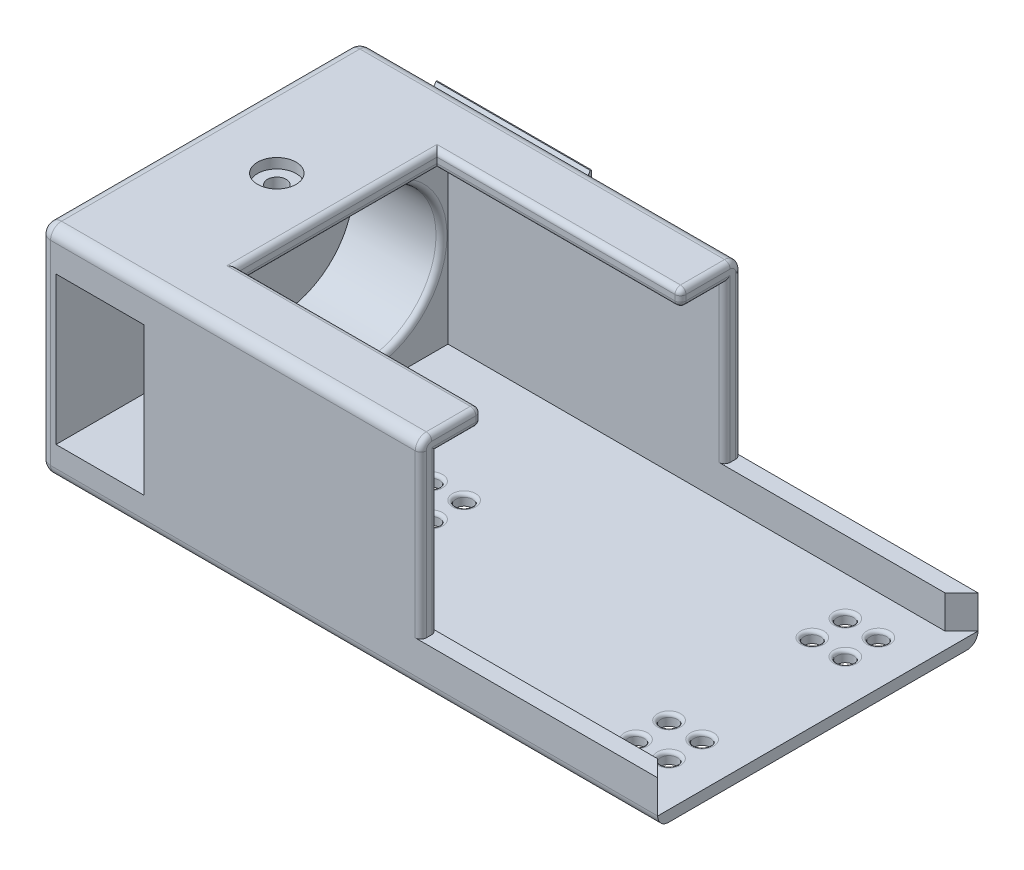
SolidWorks part; units mm, degrees
ref_plane "Front Plane" through (0, 0, 0) normal (0, 0, 1) x (1, 0, 0)
ref_plane "Top Plane" through (0, 0, 0) normal (0, 1, 0) x (1, 0, 0)
ref_plane "Right Plane" through (0, 0, 0) normal (1, 0, 0) x (0, 0, -1)
sketch "Sketch1" plane through (0, 0, 0) normal (0, 1, 0) x (1, 0, 0)
  line L1 (-26.2581, 9.1194) -> (18.3419, 9.1194) construction
  line L2 (-26.2581, 9.1194) -> (-26.2581, -16.5806) construction
  line L3 (-26.2581, -16.5806) -> (18.3419, -16.5806) construction
  line L4 (18.3419, 9.1194) -> (18.3419, -16.5806) construction
  line L5 (-26.5081, 9.2444) -> (18.5919, 9.2444)
  line L6 (-26.5081, 9.2444) -> (-26.5081, -16.8306)
  line L7 (-26.5081, -16.8306) -> (18.5919, -16.8306)
  line L8 (18.5919, 9.2444) -> (18.5919, -16.8306)
  line L9 (-28.0081, 10.7444) -> (20.0919, 10.7444)
  line L10 (-28.0081, 10.7444) -> (-28.0081, -18.3306)
  line L11 (-28.0081, -18.3306) -> (20.0919, -18.3306)
  line L12 (20.0919, 10.7444) -> (20.0919, -18.3306)
  dimension "D1" = 25.7
  dimension "D2" = 44.6
  dimension "D3" = 0.25
  dimension "D4" = 0.25
  dimension "D5" = 0.25
  dimension "D6" = 0.25
  dimension "D7" = 1.5
  dimension "D8" = 1.5
  dimension "D9" = 1.5
  dimension "D10" = 1.5
extrude "Boss-Extrude1" add sketch "Sketch1" along normal blind 1 contours L10 L11 L12 L9
sketch "Sketch3" plane through (0, 1, 0) normal (0, 1, 0) x (1, 0, 0)
  line L0 (-28.0081, 10.7444) -> (20.0919, 10.7444) construction
  line L1 (-26.5081, 9.2444) -> (18.5919, 9.2444)
  line L2 (-26.5081, 9.2444) -> (-26.5081, -16.8306)
  line L3 (-26.5081, -16.8306) -> (18.5919, -16.8306)
  line L5 (-28.0081, 10.7444) -> (-28.0081, -18.3306) construction
  line L7 (-28.0081, -18.3306) -> (20.0919, -18.3306) construction
  line L8 (18.5919, 9.2444) -> (20.0919, 10.7444)
  line L9 (-28.0081, 10.7444) -> (20.0919, 10.7444)
  line L10 (-28.0081, 10.7444) -> (-28.0081, -18.3306)
  line L11 (-28.0081, -18.3306) -> (20.0919, -18.3306)
  line L13 (18.5919, -16.8306) -> (20.0919, -18.3306)
  dimension "D1" = 1.5
  dimension "D2" = 1.5
  dimension "D4" = 1.5
extrude "Boss-Extrude3" add sketch "Sketch3" along normal blind 3
sketch "Sketch6" plane through (0, 4, 0) normal (0, 1, 0) x (1, 0, 0)
  line L0 (-28.0081, -18.3306) -> (20.0919, -18.3306) construction
  line L1 (-28.0081, 10.7444) -> (-1.4081, 10.7444)
  line L2 (-28.0081, 10.7444) -> (-28.0081, -18.3306)
  line L3 (-28.0081, -18.3306) -> (-1.4081, -18.3306)
  line L4 (-1.4081, 10.7444) -> (-1.4081, 9.2444)
  line L5 (-26.5081, -16.8306) -> (-26.5081, 9.2444) construction
  line L6 (-26.5081, 9.2444) -> (-1.4081, 9.2444)
  line L7 (-26.5081, 9.2444) -> (-26.5081, -16.8306)
  line L8 (-26.5081, -16.8306) -> (-1.4081, -16.8306)
  line L10 (-26.5081, -16.8306) -> (-26.5081, 9.2444) construction
  line L11 (18.5919, -16.8306) -> (-26.5081, -16.8306) construction
  line L12 (-26.5081, 9.2444) -> (18.5919, 9.2444) construction
  line L13 (-1.4081, -16.8306) -> (-1.4081, -18.3306)
  dimension "D1" = 20
extrude "Boss-Extrude4" add sketch "Sketch6" along normal blind 17.2 from surface at -3 starting at face at (4.0585, 1, 3.7931)
sketch "Sketch7" plane through (0, 18.2, 0) normal (0, 1, 0) x (1, 0, 0)
  line L0 (-1.4081, -18.3306) -> (-28.0081, -18.3306) construction
  line L1 (-28.0081, 10.7444) -> (-1.4081, 10.7444)
  line L2 (-28.0081, 10.7444) -> (-28.0081, -18.3306)
  line L3 (-28.0081, -18.3306) -> (-1.4081, -18.3306)
  line L4 (-1.4081, 10.7444) -> (-1.4081, -18.3306)
  line L5 (-1.4081, -16.8306) -> (-1.4081, -18.3306) construction
extrude "Boss-Extrude5" add sketch "Sketch7" along normal blind 1.5
sketch "Sketch8" plane through (-28.0081, 0, 0) normal (-1, 0, 0) x (0, 0, 1)
  line L0 (-9.2444, 1) -> (16.8306, 1) construction
  line L3 (16.8306, 18.2) -> (-9.2444, 18.2) construction
  line L4 (-10.7444, 19.7) -> (-10.7444, 0) construction
  line L5 (18.3306, 19.7) -> (18.3306, 0) construction
  line L6 (-10.7444, 19.7) -> (18.3306, 19.7) construction
  line L7 (-10.7444, 0) -> (18.3306, 0) construction
  line L8 (-9.2444, 18.2) -> (-9.2444, 1) construction
  line L9 (16.8306, 18.2) -> (16.8306, 1) construction
  line L10 (3.7931, 18.2) -> (3.7931, 1) construction
  line L11 (-9.2444, 9.6) -> (16.8306, 9.6) construction
  line L12 (-8.6569, 9.6) -> (16.2431, 9.6) construction
  line L15 (-1.9569, 9.6) -> (9.5431, 9.6) construction
  line L16 (-1.9569, 16.3) -> (9.5431, 16.3)
  line L17 (-1.9569, 2.9) -> (9.5431, 2.9)
  line L19 (9.5431, 16.3) -> (18.3306, 16.3)
  line L20 (9.5431, 16.3) -> (9.5431, 2.9) construction
  line L21 (9.5431, 2.9) -> (18.3306, 2.9)
  line L22 (18.3306, 16.3) -> (18.3306, 2.9)
  arc A2 (-1.9569, 16.3) -> (-1.9569, 2.9) centre (-1.9569, 9.6) ccw
  point P15 (3.7931, 18.2)
  point P18 (3.7931, 19.7)
  point P29 (3.7931, 9.6)
  dimension "D3" = 1.5
  dimension "D4" = 1.5
  dimension "D5" = 1.5
  dimension "D1" = 1
  dimension "D2" = 1.5
  dimension "D6" = 1.5
  dimension "D9" = 13.4
  dimension "D7" = 24.9
  dimension "D8" = 0.5875
  dimension "D10" = 1.9
  dimension "D11" = 7.2875
extrude "Cut-Extrude2" cut sketch "Sketch8" against normal blind 1.5
sketch "Sketch17" plane through (-28.0081, 0, 0) normal (-1, 0, 0) x (0, 0, 1)
  line L1 (-10.7444, 19.7) -> (18.3306, 19.7)
  line L2 (-10.7444, 19.7) -> (-10.7444, 0)
  line L3 (-10.7444, 0) -> (18.3306, 0)
  line L4 (18.3306, 19.7) -> (18.3306, 0)
  line L5 (-1.9569, 16.3) -> (18.3306, 16.3)
  line L7 (-1.9569, 2.9) -> (18.3306, 2.9)
  line L8 (18.3306, 16.3) -> (18.3306, 2.9)
  arc A0 (-1.9569, 16.3) -> (-1.9569, 2.9) centre (-1.9569, 9.6) ccw
  arc M6 (-1.9569, 2.9) -> (-1.9569, 16.3) centre (-1.9569, 9.6) cw
  line M7 (-1.9569, 16.3) -> (18.3306, 16.3)
  line M8 (18.3306, 16.3) -> (18.3306, 19.7)
  line M9 (18.3306, 19.7) -> (-10.7444, 19.7)
  line M10 (-10.7444, 19.7) -> (-10.7444, 0)
  line M11 (-10.7444, 0) -> (18.3306, 0)
  line M12 (18.3306, 0) -> (18.3306, 2.9)
  line M13 (18.3306, 2.9) -> (-1.9569, 2.9)
extrude "Boss-Extrude8" add sketch "Sketch17" along normal blind 6.5 contours M13 M6 M7 M8 M9 M10 M11 M12
sketch "Sketch18" plane through (-34.5081, 0, 0) normal (-1, 0, 0) x (0, 0, 1)
  line L1 (-10.7444, 19.7) -> (18.3306, 19.7)
  line L2 (-10.7444, 19.7) -> (-10.7444, 0)
  line L3 (-10.7444, 0) -> (18.3306, 0)
  line L4 (18.3306, 19.7) -> (18.3306, 0)
extrude "Boss-Extrude9" add sketch "Sketch18" along normal blind 1.5
sketch "Sketch19" plane through (0, 19.7, 0) normal (0, 1, 0) x (1, 0, 0)
  line L0 (-26.5081, -18.3306) -> (-26.5081, 10.7444) construction
  line L1 (-36.0081, -18.3306) -> (-1.4081, -18.3306) construction
  line L2 (-1.4081, 10.7444) -> (-36.0081, 10.7444) construction
  line L3 (-36.0081, -18.3306) -> (-36.0081, 10.7444) construction
  line L4 (-1.4081, -18.3306) -> (-1.4081, 10.7444) construction
  line L5 (-1.4081, 5.2444) -> (-23.5081, 5.2444)
  line L6 (-1.4081, 5.2444) -> (-1.4081, -12.8306)
  line L7 (-1.4081, -12.8306) -> (-23.5081, -12.8306)
  line L8 (-23.5081, 5.2444) -> (-23.5081, -12.8306)
  line L9 (-26.5081, 9.2444) -> (-1.4081, 9.2444) construction
  line L10 (-26.5081, -16.8306) -> (-1.4081, -16.8306) construction
  dimension "D1" = 9.5
  dimension "D2" = 1.5
  dimension "D3" = 1.5
  dimension "D4" = 3
  dimension "D5" = 4
  dimension "D6" = 4
extrude "Cut-Extrude3" cut sketch "Sketch19" against normal up to surface (1.5 mm away) contours L5 L8 L7 L6 up to face at (-13.9581, 18.2, 3.7931)
fillet "Fillet2" radius 1 8 edges at (-36.0081, 0, 3.7931) (-36.0081, 19.7, 3.7931) (-36.0081, 9.85, -10.7444) (-18.7081, 19.7, -10.7444) (-7.9581, 0, -10.7444) (-7.9581, 0, 18.3306) (-36.0081, 9.85, 18.3306) (-18.7081, 19.7, 18.3306)
fillet "Fillet3" radius 0.5 16 edges at (-1.4081, 18.2, -7.2444) (-1.4081, 19.7, -7.4944) (-12.4581, 18.2, 12.8306) (-12.4581, 19.7, 12.8306) (-12.4581, 19.7, -5.2444) (-23.5081, 19.7, 3.7931) (-23.5081, 18.2, 3.7931) (-12.4581, 18.2, -5.2444) (-1.4081, 19.7, 15.0806) (-1.4081, 11.35, -10.7444) (-1.4081, 19.4071, -10.4515) (-1.4081, 11.35, 18.3306) (-1.4081, 19.4071, 18.0377) (-1.4081, 11.1, -9.2444) (-1.4081, 11.1, 16.8306) (-1.4081, 18.2, 14.8306)
fillet "Fillet4" radius 0.5 3 edges at (-26.5081, 16.3, 7.4369) (-26.5081, 9.6, -8.6569) (-26.5081, 2.9, 7.4369)
sketch "Sketch20" plane through (0, 19.7, 0) normal (0, 1, 0) x (1, 0, 0)
  line L0 (-23.5081, 9.7444) -> (-23.5081, -17.3306) construction
  line L1 (-1.9081, 9.7444) -> (-35.0081, 9.7444) construction
  line L2 (-35.0081, -17.3306) -> (-1.9081, -17.3306) construction
  line L3 (-24.0081, -13.3306) -> (-24.0081, 5.7444) construction
  line L4 (-23.5081, -3.7931) -> (-35.0081, -3.7931) construction
  line L5 (-35.0081, 9.7444) -> (-35.0081, -17.3306) construction
  line L6 (-26.5081, -17.3306) -> (-26.5081, 9.7444) construction
  circle A0 centre (-29.0081, -3.7931) radius 0.85
  dimension "D3" = 1.7
  dimension "D1" = 0.5
  dimension "D2" = 3
  dimension "D4" = 2.5
extrude "Cut-Extrude4" cut sketch "Sketch20" against normal offset from surface (17.8 mm away) 1 contours A0 up to face at (-29.3415, 2.9, 11.0681) offset beyond the face yes
sketch "Sketch22" plane through (0, 1, 0) normal (0, 1, 0) x (1, 0, 0)
  line L0 (-26.5081, 9.2444) -> (18.5919, 9.2444) construction
  line L1 (16.0919, 5.7044) -> (13.0919, 5.7044) construction
  line L2 (16.0919, 5.7044) -> (16.0919, 2.7044) construction
  line L3 (16.0919, 2.7044) -> (13.0919, 2.7044) construction
  line L4 (13.0919, 5.7044) -> (13.0919, 2.7044) construction
  line L5 (16.0919, -10.2956) -> (13.0919, -10.2956) construction
  line L6 (16.0919, -10.2956) -> (16.0919, -13.2956) construction
  line L7 (16.0919, -13.2956) -> (13.0919, -13.2956) construction
  line L8 (13.0919, -10.2956) -> (13.0919, -13.2956) construction
  line L9 (-13.5081, -2.2956) -> (-16.5081, -2.2956) construction
  line L10 (-13.5081, -2.2956) -> (-13.5081, -5.2956) construction
  line L11 (-13.5081, -5.2956) -> (-16.5081, -5.2956) construction
  line L12 (-16.5081, -2.2956) -> (-16.5081, -5.2956) construction
  line L13 (18.5919, -16.8306) -> (-26.5081, -16.8306) construction
  line L14 (20.0919, 10.7444) -> (20.0919, -18.3306) construction
  line L15 (-26.5081, -16.8306) -> (-26.5081, 9.2444) construction
  circle A1 centre (13.0919, 2.7044) radius 0.75
  circle A2 centre (16.0919, 2.7044) radius 0.75
  circle A3 centre (16.0919, 5.7044) radius 0.75
  circle A4 centre (13.0919, 5.7044) radius 0.75
  circle A5 centre (16.0919, -10.2956) radius 0.75
  circle A6 centre (16.0919, -13.2956) radius 0.75
  circle A7 centre (13.0919, -10.2956) radius 0.75
  circle A8 centre (13.0919, -13.2956) radius 0.75
  circle A9 centre (-13.5081, -2.2956) radius 0.75
  circle A10 centre (-13.5081, -5.2956) radius 0.75
  circle A11 centre (-16.5081, -5.2956) radius 0.75
  circle A12 centre (-16.5081, -2.2956) radius 0.75
  point P12 (-13.5081, -3.7956)
  point P17 (13.0919, 4.2044)
  point P18 (13.0919, -11.7956)
  dimension "D12" = 1.5
  dimension "D13" = 1.5
  dimension "D14" = 1.5
  dimension "D15" = 1.5
  dimension "D16" = 1.5
  dimension "D17" = 1.5
  dimension "D18" = 1.5
  dimension "D19" = 1.5
  dimension "D20" = 1.5
  dimension "D21" = 1.5
  dimension "D22" = 1.5
  dimension "D23" = 1.5
  dimension "D1" = 13.04
  dimension "D2" = 13.035
  dimension "D3" = 8
  dimension "D5" = 3
  dimension "D6" = 3
  dimension "D7" = 8
  dimension "D9" = 4
  dimension "D10" = 4
  dimension "D11" = 3
  dimension "D8" = 10
extrude "Cut-Extrude5" cut sketch "Sketch22" against normal up to surface (1 mm away) up to face at (-7.4581, 0, 3.7931)
sketch "Sketch23" plane through (0, 19.7, 0) normal (0, 1, 0) x (1, 0, 0)
  circle A0 centre (-29.0081, -3.7931) radius 1.75
  dimension "D1" = 3.5
extrude "Cut-Extrude6" cut sketch "Sketch23" against normal blind 0.9 contours A0
fillet "Fillet6" radius 0.3 12 edges at (16.0919, 1, 14.0456) (13.0919, 1, 14.0456) (13.0919, 1, 11.0456) (16.0919, 1, 11.0456) (16.0919, 1, -1.9544) (16.0919, 1, -4.9544) (13.0919, 1, -4.9544) (13.0919, 1, -1.9544) (-13.5081, 1, 6.0456) (-16.5081, 1, 6.0456) (-13.5081, 1, 3.0456) (-16.5081, 1, 3.0456)
fillet "Fillet7" radius 0.5 6 edges at (-1.4081, 18.95, -5.2444) (-1.4081, 18.95, 12.8306) (-1.5546, 19.5536, 12.9771) (-1.5546, 19.5536, -5.3908) (-1.5546, 18.3464, 12.9771) (-1.5546, 18.3464, -5.3908)
sketch "Sketch24" plane through (0, 0, -10.7444) normal (0, 0, -1) x (-1, 0, 0)
  line L0 (35.0081, 1) -> (35.0081, 18.7) construction
  line L1 (35.0081, 13.7) -> (21.0081, 13.7)
  line L2 (35.0081, 13.7) -> (35.0081, 11.7)
  line L3 (35.0081, 11.7) -> (21.0081, 11.7)
  line L4 (21.0081, 13.7) -> (21.0081, 11.7)
  line L5 (35.0081, 18.7) -> (1.9081, 18.7) construction
  dimension "D1" = 14
  dimension "D2" = 5
  dimension "D3" = 2
extrude "Boss-Extrude10" add sketch "Sketch24" along normal blind 6
sketch "Sketch25" plane through (-35.0081, 0, 0) normal (-1, 0, 0) x (0, 0, 1)
  line L0 (-16.7444, 11.7) -> (-10.7444, 11.7) construction
  line L1 (-13.9444, 11.7) -> (-13.9444, 17.5454) construction
  line L2 (-10.7444, 13.7) -> (-10.7444, 18.7) construction
  circle A0 centre (-13.9444, 15.2) radius 3.1
  dimension "D1" = 6.2
  dimension "D2" = 3.5
  dimension "D3" = 3.2
extrude "Cut-Extrude7" cut sketch "Sketch25" against normal up to surface (14 mm away) contours A0 up to face at (-21.0081, 12.7, -13.7444)
sketch "Sketch27" plane through (-35.0081, 0, 0) normal (-1, 0, 0) x (0, 0, 1)
  line L0 (-16.7444, 11.7) -> (-10.7444, 1)
  line L1 (-9.7444, 1) -> (-10.7444, 1) construction
  line L2 (-10.7444, 1) -> (-10.7444, 11.7) construction
  line L3 (-10.7444, 1) -> (-10.7444, 11.7)
  line L4 (-16.7444, 11.7) -> (-10.7444, 11.7) construction
  line L5 (-10.7444, 11.7) -> (-16.7444, 11.7)
extrude "Boss-Extrude11" add sketch "Sketch27" against normal up to surface (14 mm away) up to face at (-21.0081, 12.7667, -13.811)
equation "\"D1@Boss-Extrude4\"=16.7 + 0.5mm"
equation "\"D9@Sketch8\"=12.9+0.5"
equation "\"D4@Sketch20\"=2.5"
equation "\"HOLE_DIMENSION\"=1.5"
equation "\"D13@Sketch22\"=\"HOLE_DIMENSION\""
equation "\"D15@Sketch22\"=\"HOLE_DIMENSION\""
equation "\"D12@Sketch22\"=\"HOLE_DIMENSION\""
equation "\"D14@Sketch22\"=\"HOLE_DIMENSION\""
equation "\"D16@Sketch22\"=\"HOLE_DIMENSION\""
equation "\"D17@Sketch22\"=\"HOLE_DIMENSION\""
equation "\"D18@Sketch22\"=\"HOLE_DIMENSION\""
equation "\"D19@Sketch22\"=\"HOLE_DIMENSION\""
equation "\"D20@Sketch22\"=\"HOLE_DIMENSION\""
equation "\"D21@Sketch22\"=\"HOLE_DIMENSION\""
equation "\"D22@Sketch22\"=\"HOLE_DIMENSION\""
equation "\"D23@Sketch22\"=\"HOLE_DIMENSION\""
equation "\"PIN_HOLE_DIAMETER\"=1.7"
equation "\"D3@Sketch20\"=\"PIN_HOLE_DIAMETER\""
